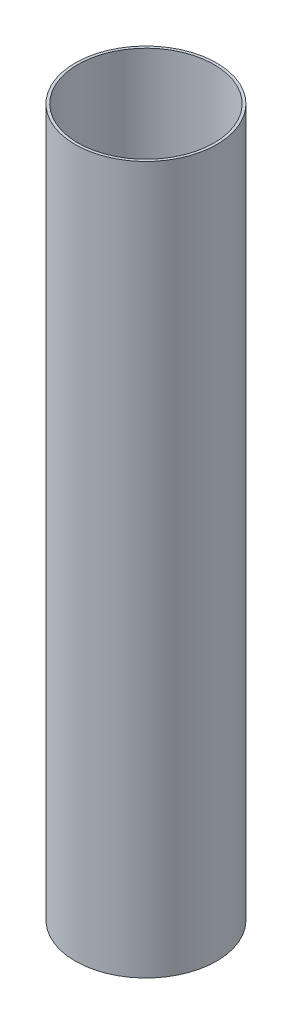
SolidWorks part; units mm, degrees
ref_plane "Спереди" through (0, 0, 0) normal (0, 0, 1) x (1, 0, 0)
ref_plane "Сверху" through (0, 0, 0) normal (0, 1, 0) x (1, 0, 0)
ref_plane "Справа" through (0, 0, 0) normal (1, 0, 0) x (0, 0, -1)
sketch "Эскиз1" plane through (0, 0, 0) normal (0, 1, 0) x (1, 0, 0)
  circle A0 centre (0, 0) radius 80
extrude "Вытянуть-Тонкостенный1" add sketch "Эскиз1" along normal blind 800 thin thin type one direction reverse wall 3
